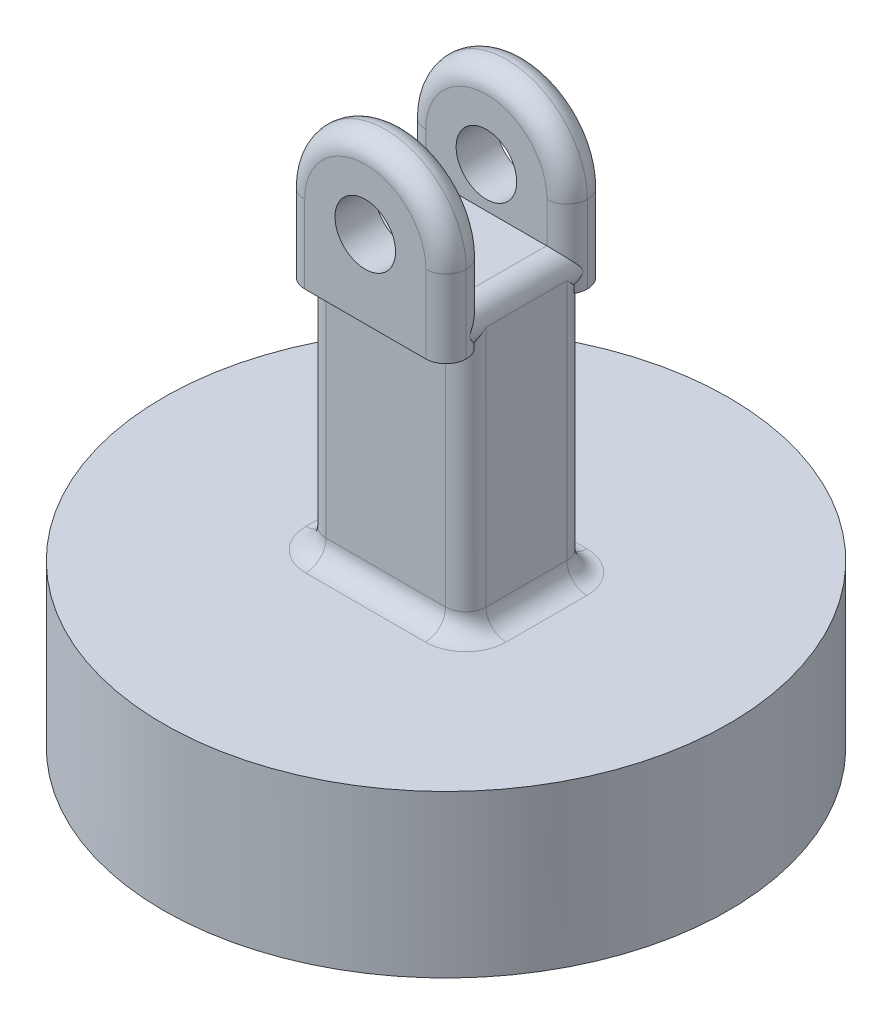
SolidWorks part; units mm, degrees
ref_plane "Front Plane" through (0, 0, 0) normal (0, 0, 1) x (1, 0, 0)
ref_plane "Top Plane" through (0, 0, 0) normal (0, 1, 0) x (1, 0, 0)
ref_plane "Right Plane" through (0, 0, 0) normal (1, 0, 0) x (0, 0, -1)
sketch "Sketch1" plane through (0, 0, 0) normal (0, 1, 0) x (1, 0, 0)
  circle A0 centre (0, 0) radius 7
  dimension "D1" = 14
extrude "Boss-Extrude1" add sketch "Sketch1" along normal blind 10
sketch "Sketch2" plane through (0, 10, 0) normal (0, 1, 0) x (1, 0, 0)
  line L0 (-7, 0) -> (7, 0)
  line L1 (0, 0) -> (0, 7)
  line L2 (0, 7) -> (0, -7)
  line L4 (0, 0) -> (2, 0)
  line L5 (0, 0) -> (0, 2)
  line L6 (0, 2) -> (2, 2)
  line L7 (2, 0) -> (2, 2)
  line L8 (0, 0) -> (2, 0)
  line L9 (0, 0) -> (0, -2)
  line L10 (0, -2) -> (2, -2)
  line L11 (2, 0) -> (2, -2)
  line L12 (0, -2) -> (-2, -2)
  line L13 (0, -2) -> (0, 0)
  line L14 (0, 0) -> (-2, 0)
  line L15 (-2, -2) -> (-2, 0)
  line L16 (-2, 0) -> (0, 0)
  line L17 (-2, 0) -> (-2, 2)
  line L18 (-2, 2) -> (0, 2)
  line L19 (0, 0) -> (0, 2)
  line L20 (-2, 2) -> (2, 2)
  line L21 (-2, 2) -> (-2, 1)
  line L22 (-2, 1) -> (2, 1)
  line L23 (2, 2) -> (2, 1)
  line L24 (2, -2) -> (-2, -2)
  line L25 (2, -2) -> (2, -1)
  line L26 (2, -1) -> (-2, -1)
  line L27 (-2, -2) -> (-2, -1)
  circle A0 centre (0, 0) radius 7 construction
  dimension "D1" = 2
  dimension "D2" = 2
  dimension "D3" = 2
  dimension "D4" = 2
  dimension "D5" = 2
  dimension "D6" = 2
  dimension "D7" = 2
  dimension "D8" = 2
  dimension "D9" = 1
  dimension "D10" = 1
extrude "Boss-Extrude2" add sketch "Sketch2" along normal blind 4 contours L17 L22 L19 L18 | L19 L22 L7 L6 | L11 L26 L13 L10 | L13 L26 L15 L12
sketch "Sketch3" plane through (0, 0, 2) normal (0, 0, 1) x (1, 0, 0)
  line L0 (-2, 14) -> (2, 10)
  circle A0 centre (0, 12) radius 2
  circle A1 centre (0, 12) radius 0.75
  line M2 (2, 10) -> (2, 14)
  line M3 (2, 14) -> (-2, 14)
  line M4 (-2, 14) -> (-2, 10)
  dimension "D1" = 4
  dimension "D2" = 1.5
extrude "Cut-Extrude2" cut sketch "Sketch3" against normal blind 10 contours A0 M2 M3 | A0 L0 M3 | A0 L0 M4 | L0 A1 | L0 A1
fillet "Fillet1" radius 1 1 edges at (0, 10, 7)
fillet "Fillet2" radius 0.5 12 edges at (2, 11, 1) (-2, 11, 1) (2, 11, 2) (-2, 11, 2) (-2, 11, -2) (2, 11, -2) (-2, 11, -1) (2, 11, -1) (0, 14, 1) (0, 14, 2) (0, 14, -2) (0, 14, -1)
sketch "Sketch4" plane through (0, 0, 0) normal (0, 0, 1) x (1, 0, 0)
  line L0 (-7, 9) -> (-7, 0) construction
  line L1 (7, 0) -> (-7, 0)
  line L2 (7, 0) -> (7, 4)
  line L3 (7, 4) -> (-7, 4)
  line L4 (-7, 0) -> (-7, 4)
  line L6 (-7.8704, 4) -> (9.3236, 4)
  line L7 (-7.8704, 4) -> (-7.8704, 10.077)
  line L8 (-7.8704, 10.077) -> (9.3236, 10.077)
  line L9 (9.3236, 4) -> (9.3236, 10.077)
  dimension "D1" = 4
extrude "Cut-Extrude4" cut sketch "Sketch4" against normal mid plane 20 contours L6 L9 L8 L7 L3
sketch "Sketch5" plane through (0, 4, 0) normal (0, 1, 0) x (1, 0, 0)
  line L0 (-2, 1.5) -> (2, 1.5) construction
  line L1 (-1.97, 1.5) -> (1.9895, 1.5)
  line L2 (-1.97, 1.5) -> (-1.97, -1.5)
  line L3 (-1.97, -1.5) -> (1.9895, -1.5)
  line L4 (1.9895, 1.5) -> (1.9895, -1.5)
  line L5 (-2, -1.5) -> (2, -1.5) construction
extrude "Boss-Extrude3" add sketch "Sketch5" along normal blind 7
fillet "Fillet3" radius 0.5 2 edges at (-1.97, 11, 0) (1.9895, 11, 0)
fillet "Fillet4" radius 0.5 8 edges at (-1.97, 4, 0) (-1.97, 7.0385, 1.5) (-1.97, 7.0385, -1.5) (0.0098, 4, -1.5) (0.0098, 4, 1.5) (1.9895, 4, 0) (1.9895, 7.0385, -1.5) (1.9895, 7.0385, 1.5)
